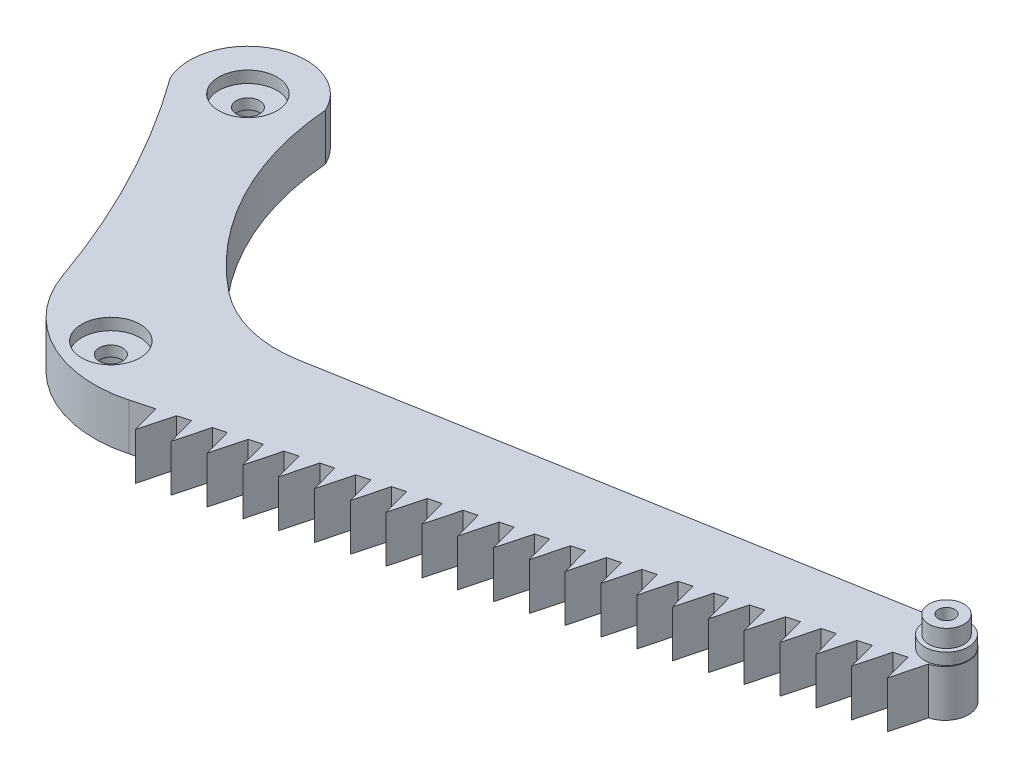
SolidWorks part; units mm, degrees
ref_plane "Front Plane" through (0, 0, 0) normal (0, 0, 1) x (1, 0, 0)
ref_plane "Top Plane" through (0, 0, 0) normal (0, 1, 0) x (1, 0, 0)
ref_plane "Right Plane" through (0, 0, 0) normal (1, 0, 0) x (0, 0, -1)
sketch "Sketch1" plane through (0, 0, 0) normal (0, 1, 0) x (1, 0, 0)
  line L0 (-146.8741, 0) -> (146.8741, 0)
  line L1 (-146.8741, 0) -> (0, -40)
  line L2 (0, -40) -> (146.8741, 0)
  line L3 (-117.1308, -3.9158) -> (-146.8741, 0) construction
  line L4 (117.1308, -3.9158) -> (146.8741, 0) construction
  line L5 (0, -30) -> (0, -40) construction
  line L6 (117.1308, -3.9158) -> (0, -30) construction
  line L7 (0, -30) -> (-117.1308, -3.9158) construction
  circle A0 centre (-117.1308, -3.9158) radius 1.4
  circle A1 centre (0, -30) radius 1.4
  circle A2 centre (117.1308, -3.9158) radius 1.4
  point P4 (0, 0)
  dimension "D2" = 2.8
  dimension "D1" = 120
  dimension "D3" = 30
  dimension "D4" = 7.5
  dimension "D5" = 10
  dimension "D6" = 40
extrude "Boss-Extrude1" add sketch "Sketch1" along normal blind 8
sketch "Sketch2" plane through (0, 8, 0) normal (0, 1, 0) x (1, 0, 0)
  circle A0 centre (117.1308, -3.9158) radius 3.75
  dimension "D1" = 7.5
extrude "Boss-Extrude2" add sketch "Sketch2" along normal blind 2
sketch "Sketch3" plane through (0, 10, 0) normal (0, 1, 0) x (1, 0, 0)
  circle A0 centre (117.1308, -3.9158) radius 3
  dimension "D1" = 6
extrude "Boss-Extrude3" add sketch "Sketch3" along normal blind 3
sketch "Sketch4" plane through (0, 13, 0) normal (0, 1, 0) x (1, 0, 0)
  circle A0 centre (117.1308, -3.9158) radius 1.4
  dimension "D1" = 2.8
extrude "Cut-Extrude1" cut sketch "Sketch4" against normal through all both and the other way through all
fillet "Fillet1" radius 4 2 edges at (-146.8741, 4, 0) (146.8741, 4, 0)
sketch "Sketch5" plane through (0, 0, 0) normal (0, -1, 0) x (1, 0, 0)
  circle A0 centre (-117.1308, 3.9158) radius 5.1
  dimension "D1" = 10.2
extrude "Cut-Extrude2" cut sketch "Sketch5" against normal blind 3.2
sketch "Sketch6" plane through (0, 3.2, 0) normal (0, -1, 0) x (1, 0, 0)
  circle A0 centre (-117.1308, 3.9158) radius 4
  dimension "D1" = 8
extrude "Cut-Extrude3" cut sketch "Sketch6" against normal blind 1
sketch "Sketch7" plane through (0, 8, 0) normal (0, 1, 0) x (1, 0, 0)
  circle A0 centre (-117.1308, -3.9158) radius 5
  dimension "D1" = 10
extrude "Cut-Extrude4" cut sketch "Sketch7" against normal blind 2
sketch "Sketch8" plane through (0, 4.2, 0) normal (0, -1, 0) x (1, 0, 0)
  circle A0 centre (-117.1308, 3.9158) radius 2
  dimension "D1" = 4
extrude "Cut-Extrude5" cut sketch "Sketch8" against normal through all both and the other way through all
sketch "Sketch9" plane through (0, 8, 0) normal (0, 1, 0) x (1, 0, 0)
  line L0 (116.9643, 0) -> (-114.0216, 0) construction
  line L1 (-10, 0) -> (-160, 0)
  line L2 (-10, 0) -> (-10, -50)
  line L3 (-10, -50) -> (-160, -50)
  line L4 (-160, 0) -> (-160, -50)
  dimension "D1" = 10
  dimension "D2" = 50
  dimension "D3" = 150
extrude "Cut-Extrude6" cut sketch "Sketch9" against normal through all
sketch "Sketch10" plane through (0, 8, 0) normal (0, 1, 0) x (1, 0, 0)
  line L0 (-10, -37.2766) -> (-38.2326, 23.2684)
  line L2 (-20.1064, 31.7208) -> (-5.3148, 0)
  line L3 (116.9643, 0) -> (-10, 0) construction
  line L4 (-10, -37.2766) -> (-10, 0)
  line L5 (-10, 0) -> (-5.3148, 0)
  line L6 (-38.2326, 23.2684) -> (-20.1064, 31.7208)
  dimension "D1" = 20
  dimension "D2" = 35
  dimension "D3" = 115
extrude "Boss-Extrude4" add sketch "Sketch10" against normal up to surface (8 mm away) up to face at (43.6838, 0, 16.9352)
fillet "Fillet2" radius 10 2 edges at (-20.1064, 4, -31.7208) (-38.2326, 4, -23.2684)
sketch "Sketch11" plane through (0, 0, 0) normal (0, -1, 0) x (1, 0, 0)
  line L0 (-34.0064, -14.2053) -> (-15.8803, -22.6577) construction
  circle A0 centre (-24.9433, -18.4315) radius 5.25
  point P2 (-24.944, -18.4315)
  dimension "D1" = 10.5
extrude "Cut-Extrude7" cut sketch "Sketch11" against normal blind 3.2
sketch "Sketch12" plane through (0, 3.2, 0) normal (0, -1, 0) x (1, 0, 0)
  circle A0 centre (-24.9433, -18.4315) radius 4
  dimension "D1" = 8
extrude "Cut-Extrude8" cut sketch "Sketch12" against normal blind 1
sketch "Sketch13" plane through (0, 8, 0) normal (0, 1, 0) x (1, 0, 0)
  circle A0 centre (-24.9433, 18.4315) radius 5
  dimension "D1" = 10
extrude "Cut-Extrude9" cut sketch "Sketch13" against normal blind 2
sketch "Sketch14" plane through (0, 4.2, 0) normal (0, -1, 0) x (1, 0, 0)
  circle A0 centre (-24.9433, -18.4315) radius 2
  dimension "D1" = 4
extrude "Cut-Extrude10" cut sketch "Sketch14" against normal through all both and the other way through all
sketch "Sketch16" plane through (0, 8, 0) normal (0, 1, 0) x (1, 0, 0)
  line L0 (-5.3148, 0) -> (3.7297, -19.396)
  line L1 (3.7297, -19.396) -> (113.7297, 0)
  line L2 (116.9643, 0) -> (-5.3148, 0) construction
  line L4 (-5.3148, 0) -> (-15.8803, 22.6577) construction
  line L5 (-5.3148, 0) -> (113.7297, 0)
  point P3 (113.3808, -0.1658)
  point P8 (70.7623, 0)
  dimension "D1" = 110
  dimension "D2" = 10
extrude "Cut-Extrude11" cut sketch "Sketch16" against normal through all both
fillet "Fillet3" radius 20 1 edges at (3.7297, 4, 19.396)
sketch "Sketch17" plane through (0, 8, 0) normal (0, 1, 0) x (1, 0, 0)
  line L0 (-34.0064, 14.2053) -> (-10, -37.2766)
  line L2 (-15.8803, 22.6577) -> (2.969, -12.7261)
  arc A0 (-34.0064, 14.2053) -> (-10, -37.2766) centre (-155.4901, -73.7816) cw
  arc A1 (-15.8803, 22.6577) -> (2.969, -12.7261) centre (33.9718, 26.5018) ccw
  arc A3 (-2.756, -5.4873) -> (18.8431, -16.7311) centre (15.3701, 2.9651) ccw construction
  dimension "D1" = 150
  dimension "D2" = 50
extrude "Cut-Extrude12" cut sketch "Sketch17" against normal through all both
fillet "Fillet4" radius 20 1 edges at (-10, 4, 37.2766)
fillet "Fillet5" radius 20 1 edges at (0, 4, 40)
sketch "Sketch18" plane through (0, 8, 0) normal (0, 1, 0) x (1, 0, 0)
  line L0 (118.0154, -7.8594) -> (116.544, -13.4423)
  line L1 (116.544, -13.4423) -> (115.2301, -8.618)
  line L2 (10.3159, -37.1905) -> (118.0154, -7.8594) construction
  line L3 (115.2301, -8.618) -> (118.0154, -7.8594)
  dimension "D1" = 5
  dimension "D2" = 60
extrude "Boss-Extrude5" add sketch "Sketch18" against normal up to surface (8 mm away) up to face at (28.4418, 0, 3.8095)
pattern_linear "LPattern1" count 22 spacing 5 along (-0.9649, 0, 0.2628) of "Boss-Extrude5"
sketch "Sketch19" plane through (0, 0, 0) normal (0, -1, 0) x (1, 0, 0)
  circle A0 centre (0, 30) radius 5.25
  dimension "D1" = 10.5
extrude "Cut-Extrude13" cut sketch "Sketch19" against normal blind 3.2
sketch "Sketch20" plane through (0, 3.2, 0) normal (0, -1, 0) x (1, 0, 0)
  circle A0 centre (0, 30) radius 4
  dimension "D1" = 8
extrude "Cut-Extrude14" cut sketch "Sketch20" against normal blind 1
sketch "Sketch21" plane through (0, 4.2, 0) normal (0, -1, 0) x (1, 0, 0)
  circle A0 centre (0, 30) radius 2
  dimension "D1" = 4
extrude "Cut-Extrude15" cut sketch "Sketch21" against normal through all both and the other way through all
sketch "Sketch22" plane through (0, 8, 0) normal (0, 1, 0) x (1, 0, 0)
  circle A0 centre (0, -30) radius 5
  dimension "D1" = 10
extrude "Cut-Extrude16" cut sketch "Sketch22" against normal blind 2
